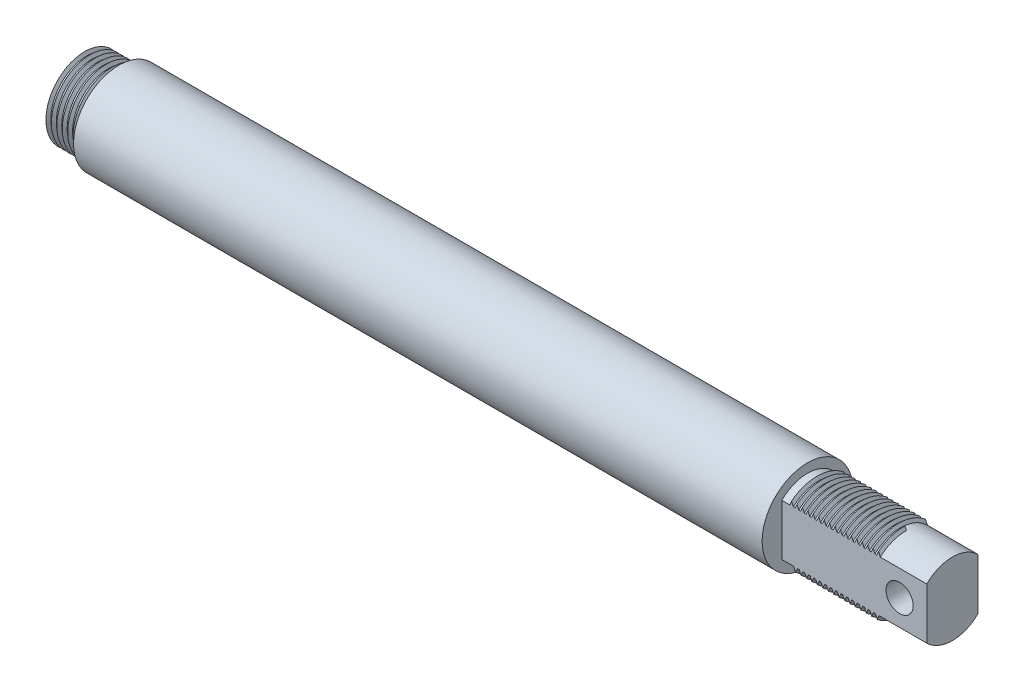
SolidWorks part; units mm, degrees
ref_plane "Front Plane" through (0, 0, 0) normal (0, 0, 1) x (1, 0, 0)
ref_plane "Top Plane" through (0, 0, 0) normal (0, 1, 0) x (1, 0, 0)
ref_plane "Right Plane" through (0, 0, 0) normal (1, 0, 0) x (0, 0, -1)
sketch "Sketch1" plane through (0, 0, 0) normal (1, 0, 0) x (0, 0, -1)
  circle A0 centre (0, 0) radius 25
extrude "Boss-Extrude1" add sketch "Sketch1" along normal blind 350
sketch "Sketch2" plane through (0, 0, 0) normal (-1, 0, 0) x (0, 0, 1)
  circle A0 centre (0, 0) radius 20
extrude "Cut-Extrude1" cut sketch "Sketch2" against normal blind 350
sketch "Sketch3" plane through (0, 0, 0) normal (-1, 0, 0) x (0, 0, 1)
  circle A0 centre (0, 0) radius 25
extrude "Boss-Extrude2" add sketch "Sketch3" along normal blind 15
sketch "Sketch5" plane through (350, 0, 0) normal (1, 0, 0) x (0, 0, -1)
  circle A0 centre (0, 0) radius 25
extrude "Boss-Extrude3" add sketch "Sketch5" along normal blind 15
sketch "Sketch6" plane through (365, 0, 0) normal (1, 0, 0) x (0, 0, -1)
  circle A0 centre (0, 0) radius 20
extrude "Boss-Extrude4" add sketch "Sketch6" along normal blind 80
sketch "Sketch7" plane through (445, 0, 0) normal (1, 0, 0) x (0, 0, -1)
  line L1 (-14.1328, -14.1514) -> (14.1328, -14.1514)
  line L2 (-14.1328, -14.1514) -> (-14.1328, 14.1514)
  line L3 (-14.1328, 14.1514) -> (14.1328, 14.1514)
  line L4 (14.1328, -14.1514) -> (14.1328, 14.1514)
  line L5 (-14.1328, -14.1514) -> (14.1328, 14.1514) construction
  line L6 (-14.1328, 14.1514) -> (14.1328, -14.1514) construction
  circle A0 centre (0, 0) radius 20 construction
  circle A1 centre (0, 0) radius 20
  point P0 (0, 0)
  circle M5 centre (0, 0) radius 20
extrude "Cut-Extrude2" cut sketch "Sketch7" against normal blind 80 contours L2 M5 | L4 M5 region at (445, 0, 16.512) region at (445, 0, -16.512)
sketch "Sketch8" plane through (0, 0, 14.1328) normal (0, 0, 1) x (1, 0, 0)
  circle A0 centre (430, 0) radius 7.5
extrude "Cut-Extrude3" cut sketch "Sketch8" against normal blind 70
ref_plane "Plane1" through (370, 0, 0) normal (1, 0, 0) x (0, 0, -1)
sketch "Sketch10" plane through (370, 0, 0) normal (1, 0, 0) x (0, 0, -1)
  circle A0 centre (0, 0) radius 20
curve "Helix/Spiral1" pitch 3 height 48.75 radius 20 left hand yes centre (370, 0, 0) axis (1, 0, 0) start towards (0, 0, 1)
sketch "Sketch12" plane through (0, 0, 0) normal (0, 0, 1) x (1, 0, 0)
  line L0 (445, 20) -> (365, 20) construction
  line L1 (418.75, 21.7) -> (417.2778, 19.15)
  line L2 (417.2778, 19.15) -> (420.2222, 19.15)
  line L3 (420.2222, 19.15) -> (418.75, 21.7)
  circle A0 centre (418.75, 20) radius 0.85 construction
  spline S0 degree 3 poles (370, 0) (370.0504, 2.1116) (370.152, 6.3652) (370.3037, 12.083) (370.4556, 16.595) (370.6075, 19.4405) (370.7593, 20.3362) (370.9112, 19.1916) (371.0631, 16.1217) (371.215, 11.4345) (371.3668, 5.6001) (371.5187, -0.7961) (371.6706, -7.1124) (371.8224, -12.7152) (371.9743, -17.0424) (372.1262, -19.6598) (372.278, -20.305) (372.4299, -18.9132) (372.5818, -15.624) (372.7336, -10.7673) (372.8855, -4.8305) (373.0374, 1.5909) (373.1893, 7.8527) (373.3411, 13.3268) (373.493, 17.4638) (373.6449, 19.8489) (373.7967, 20.2428) (373.9486, 18.6058) (374.1005, 15.1023) (374.2523, 10.0837) (374.4042, 4.0535) (374.5561, -2.3833) (374.7079, -8.5811) (374.8598, -13.9179) (375.0117, -17.8586) (375.1636, -20.0076) (375.3154, -20.1495) (375.4673, -18.2699) (375.6192, -14.5575) (375.771, -9.3847) (375.9229, -3.2703) (376.0748, 3.1721) (376.2266, 9.2962) (376.3785, 14.4878) (376.5304, 18.2259) (376.6822, 20.1356) (376.8341, 20.0253) (376.986, 17.906) (377.1379, 13.9904) (377.2897, 8.6712) (377.4416, 2.4821) (377.5935, -3.956) (377.7453, -9.9972) (377.8972, -15.0355) (378.0491, -18.5654) (378.2009, -20.2328) (378.3528, -19.8704) (378.5047, -17.5147) (378.6565, -13.4018) (378.8084, -7.9445) (378.9603, -1.6901) (379.1121, 4.7338) (379.264, 10.6828) (379.4159, 15.5601) (379.5678, 18.8764) (379.7196, 20.2989) (379.8715, 19.6851) (380.0234, 17.0965) (380.1752, 12.7927) (380.3271, 7.2055) (380.479, 0.8955) (380.6308, -5.5044) (380.7827, -11.352) (380.9346, -16.0608) (381.0864, -19.1584) (381.2383, -20.334) (381.3902, -19.4697) (381.5421, -16.6521) (381.6939, -12.164) (381.8458, -6.4556) (381.9977, -0.0995) (382.1495, 6.2665) (382.3014, 12.0039) (382.4533, 16.537) (382.6051, 19.4111) (382.757, 20.3379) (382.9089, 19.2244) (383.0607, 16.1822) (383.2126, 11.5167) (383.3645, 5.6957) (383.5164, -0.6966) (383.6682, -7.019) (383.8201, -12.6373) (383.972, -16.9878) (384.1238, -19.6341) (384.2757, -20.3106) (384.4276, -18.9496) (384.5794, -15.6875) (384.7313, -10.8517) (384.8832, -4.9272) (385.035, 1.4917) (385.1869, 7.7608) (385.3388, 13.2514) (385.4907, 17.4126) (385.6425, 19.827) (385.7944, 20.2522) (385.9463, 18.6458) (386.0981, 15.1688) (386.25, 10.17) (386.4019, 4.151) (386.5537, -2.2844) (386.7056, -8.4907) (386.8575, -13.8452) (387.0093, -17.8107) (387.1612, -19.9894) (387.3131, -20.1628) (387.465, -18.3134) (387.6168, -14.6268) (387.7687, -9.4728) (387.9206, -3.3685) (388.0724, 3.0737) (388.2243, 9.2076) (388.3762, 14.4178) (388.528, 18.1815) (388.6799, 20.1213) (388.8318, 20.0425) (388.9836, 17.953) (389.1355, 14.0624) (389.2874, 8.7611) (389.4393, 2.5809) (389.5911, -3.8583) (389.743, -9.9104) (389.8949, -14.9682) (390.0467, -18.5245) (390.1986, -20.2223) (390.3505, -19.8915) (390.5023, -17.5651) (390.6542, -13.4765) (390.8061, -8.036) (390.9579, -1.7893) (391.1098, 4.6369) (391.2617, 10.5979) (391.4136, 15.4958) (391.5654, 18.8391) (391.7173, 20.2924) (391.8692, 19.7099) (392.021, 17.1502) (392.1729, 12.8699) (392.3248, 7.2985) (392.4766, 0.9949) (392.6285, -5.4085) (392.7804, -11.2693) (392.9322, -15.9996) (393.0841, -19.1248) (393.236, -20.3313) (393.3879, -19.4982) (393.5397, -16.7091) (393.6916, -12.2436) (393.8435, -6.5499) (393.9953, -0.1991) (394.1472, 6.1717) (394.2991, 11.9234) (394.4509, 16.4788) (394.6028, 19.3811) (394.7547, 20.3391) (394.9065, 19.2566) (395.0584, 16.2423) (395.2103, 11.5986) (395.3621, 5.7912) (395.514, -0.5971) (395.6659, -6.9255) (395.8178, -12.5592) (395.9696, -16.9329) (396.1215, -19.6078) (396.2734, -20.3157) (396.4252, -18.9855) (396.5771, -15.7507) (396.729, -10.9357) (396.8808, -5.0237) (397.0327, 1.3924) (397.1846, 7.6687) (397.3364, 13.1757) (397.4883, 17.361) (397.6402, 19.8045) (397.7921, 20.2612) (397.9439, 18.6853) (398.0958, 15.2349) (398.2477, 10.2561) (398.3995, 4.2484) (398.5514, -2.1855) (398.7033, -8.4002) (398.8551, -13.7721) (399.007, -17.7624) (399.1589, -19.9708) (399.3107, -20.1757) (399.4626, -18.3565) (399.6145, -14.6958) (399.7664, -9.5608) (399.9182, -3.4667) (400.0701, 2.9753) (400.222, 9.1187) (400.3738, 14.3474) (400.5257, 18.1367) (400.6776, 20.1065) (400.8294, 20.0592) (400.9813, 17.9996) (401.1332, 14.1342) (401.285, 8.8508) (401.4369, 2.6796) (401.5888, -3.7605) (401.7407, -9.8233) (401.8925, -14.9007) (402.0444, -18.4832) (402.1963, -20.2114) (402.3481, -19.912) (402.5, -17.615) (402.6519, -13.5509) (402.8037, -8.1273) (402.9556, -1.8884) (403.1075, 4.54) (403.2593, 10.5129) (403.4112, 15.4311) (403.5631, 18.8013) (403.715, 20.2853) (403.8668, 19.7343) (404.0187, 17.2035) (404.1706, 12.9468) (404.3224, 7.3913) (404.4743, 1.0943) (404.6262, -5.3125) (404.778, -11.1863) (404.9299, -15.9379) (405.0818, -19.0906) (405.2336, -20.3282) (405.3855, -19.5263) (405.5374, -16.7656) (405.6893, -12.323) (405.8411, -6.644) (405.993, -0.2986) (406.1449, 6.0768) (406.2967, 11.8426) (406.4486, 16.4203) (406.6005, 19.3507) (406.7523, 20.3398) (406.9042, 19.2885) (407.0561, 16.302) (407.2079, 11.6802) (407.3598, 5.8866) (407.5117, -0.4976) (407.6636, -6.8319) (407.8154, -12.4807) (407.9673, -16.8775) (408.1192, -19.5811) (408.271, -20.3204) (408.4229, -19.021) (408.5748, -15.8135) (408.7266, -11.0195) (408.8785, -5.12) (409.0304, 1.2931) (409.1822, 7.5764) (409.3341, 13.0998) (409.486, 17.3089) (409.6379, 19.7816) (409.7897, 20.2698) (409.9416, 18.7244) (410.0935, 15.3007) (410.2453, 10.342) (410.3972, 4.3457) (410.5491, -2.0865) (410.7009, -8.3094) (410.8528, -13.6987) (411.0047, -17.7137) (411.1565, -19.9517) (411.3084, -20.1881) (411.4603, -18.3992) (411.6121, -14.7645) (411.764, -9.6485) (411.9159, -3.5647) (412.0678, 2.8768) (412.2196, 9.0297) (412.3715, 14.2767) (412.5234, 18.0914) (412.6752, 20.0912) (412.8271, 20.0755) (412.979, 18.0457) (413.1308, 14.2056) (413.2827, 8.9404) (413.4346, 2.7782) (413.5864, -3.6626) (413.7383, -9.7361) (413.8902, -14.8327) (414.0421, -18.4414) (414.1939, -20.2) (414.3458, -19.9321) (414.4977, -17.6646) (414.6495, -13.625) (414.8014, -8.2185) (414.9533, -1.9875) (415.1051, 4.4429) (415.257, 10.4275) (415.4089, 15.3661) (415.5607, 18.7631) (415.7126, 20.2778) (415.8645, 19.7582) (416.0164, 17.2564) (416.1682, 13.0235) (416.3201, 7.484) (416.472, 1.1937) (416.6238, -5.2163) (416.7757, -11.103) (416.9276, -15.8759) (417.0794, -19.0561) (417.2313, -20.3245) (417.3832, -19.554) (417.535, -16.8218) (417.6869, -12.402) (417.8388, -6.738) (417.9907, -0.3981) (418.1425, 5.9818) (418.2944, 11.7615) (418.4463, 16.3614) (418.598, 19.3198) (418.6996, 20) (418.75, 20) knots 0 0 0 0 0.003115 0.006231 0.009346 0.012461 0.015576 0.018692 0.021807 0.024922 0.028037 0.031153 0.034268 0.037383 0.040498 0.043614 0.046729 0.049844 0.05296 0.056075 0.05919 0.062305 0.065421 0.068536 0.071651 0.074766 0.077882 0.080997 0.084112 0.087227 0.090343 0.093458 0.096573 0.099688 0.102804 0.105919 0.109034 0.11215 0.115265 0.11838 0.121495 0.124611 0.127726 0.130841 0.133956 0.137072 0.140187 0.143302 0.146417 0.149533 0.152648 0.155763 0.158879 0.161994 0.165109 0.168224 0.17134 0.174455 0.17757 0.180685 0.183801 0.186916 0.190031 0.193146 0.196262 0.199377 0.202492 0.205607 0.208723 0.211838 0.214953 0.218069 0.221184 0.224299 0.227414 0.23053 0.233645 0.23676 0.239875 0.242991 0.246106 0.249221 0.252336 0.255452 0.258567 0.261682 0.264798 0.267913 0.271028 0.274143 0.277259 0.280374 0.283489 0.286604 0.28972 0.292835 0.29595 0.299065 0.302181 0.305296 0.308411 0.311526 0.314642 0.317757 0.320872 0.323988 0.327103 0.330218 0.333333 0.336449 0.339564 0.342679 0.345794 0.34891 0.352025 0.35514 0.358255 0.361371 0.364486 0.367601 0.370717 0.373832 0.376947 0.380062 0.383178 0.386293 0.389408 0.392523 0.395639 0.398754 0.401869 0.404984 0.4081 0.411215 0.41433 0.417445 0.420561 0.423676 0.426791 0.429907 0.433022 0.436137 0.439252 0.442368 0.445483 0.448598 0.451713 0.454829 0.457944 0.461059 0.464174 0.46729 0.470405 0.47352 0.476636 0.479751 0.482866 0.485981 0.489097 0.492212 0.495327 0.498442 0.501558 0.504673 0.507788 0.510903 0.514019 0.517134 0.520249 0.523364 0.52648 0.529595 0.53271 0.535826 0.538941 0.542056 0.545171 0.548287 0.551402 0.554517 0.557632 0.560748 0.563863 0.566978 0.570093 0.573209 0.576324 0.579439 0.582555 0.58567 0.588785 0.5919 0.595016 0.598131 0.601246 0.604361 0.607477 0.610592 0.613707 0.616822 0.619938 0.623053 0.626168 0.629283 0.632399 0.635514 0.638629 0.641745 0.64486 0.647975 0.65109 0.654206 0.657321 0.660436 0.663551 0.666667 0.669782 0.672897 0.676012 0.679128 0.682243 0.685358 0.688474 0.691589 0.694704 0.697819 0.700935 0.70405 0.707165 0.71028 0.713396 0.716511 0.719626 0.722741 0.725857 0.728972 0.732087 0.735202 0.738318 0.741433 0.744548 0.747664 0.750779 0.753894 0.757009 0.760125 0.76324 0.766355 0.76947 0.772586 0.775701 0.778816 0.781931 0.785047 0.788162 0.791277 0.794393 0.797508 0.800623 0.803738 0.806854 0.809969 0.813084 0.816199 0.819315 0.82243 0.825545 0.82866 0.831776 0.834891 0.838006 0.841121 0.844237 0.847352 0.850467 0.853583 0.856698 0.859813 0.862928 0.866044 0.869159 0.872274 0.875389 0.878505 0.88162 0.884735 0.88785 0.890966 0.894081 0.897196 0.900312 0.903427 0.906542 0.909657 0.912773 0.915888 0.919003 0.922118 0.925234 0.928349 0.931464 0.934579 0.937695 0.94081 0.943925 0.94704 0.950156 0.953271 0.956386 0.959502 0.962617 0.965732 0.968847 0.971963 0.975078 0.978193 0.981308 0.984424 0.987539 0.990654 0.993769 0.996885 1 1 1 1 construction
sweep "Sweep1" add profiles "Sketch12" path "Helix/Spiral1"
sketch "Sketch13" plane through (445, 0, 0) normal (1, 0, 0) x (0, 0, -1)
  line L1 (14.1328, 26.4625) -> (-14.1328, 26.4625)
  line L2 (14.1328, 26.4625) -> (14.1328, -26.4625)
  line L3 (14.1328, -26.4625) -> (-14.1328, -26.4625)
  line L4 (-14.1328, 26.4625) -> (-14.1328, -26.4625)
  line L5 (14.1328, 26.4625) -> (-14.1328, -26.4625) construction
  line L6 (14.1328, -26.4625) -> (-14.1328, 26.4625) construction
  circle A0 centre (0, 0) radius 30
  line M2 (14.1328, -14.1514) -> (14.1328, 14.1514)
  line M4 (-14.1328, 14.1514) -> (-14.1328, -14.1514)
extrude "Cut-Extrude4" cut sketch "Sketch13" against normal blind 80 contours L4 A0 M4 | L2 A0 M2 region at (445, 0, -20.6499) region at (445, 0, 20.6499)
sketch "Sketch14" plane through (-15, 0, 0) normal (-1, 0, 0) x (0, 0, 1)
  circle A0 centre (0, 0) radius 20
extrude "Boss-Extrude5" add sketch "Sketch14" along normal blind 20
sketch "Sketch15" plane through (-35, 0, 0) normal (-1, 0, 0) x (0, 0, 1)
  circle A0 centre (0, 0) radius 20
curve "Helix/Spiral2" pitch 3 height 17.25 radius 20 centre (-35, 0, 0) axis (1, 0, 0) start towards (0, 0, -1)
sketch "Sketch16" plane through (0, 0, 0) normal (0, 0, 1) x (1, 0, 0)
  line L0 (-35, -20) -> (-15, -20) construction
  line L1 (-17.75, -21.7) -> (-16.2778, -19.15)
  line L2 (-16.2778, -19.15) -> (-19.2222, -19.15)
  line L3 (-19.2222, -19.15) -> (-17.75, -21.7)
  circle A0 centre (-17.75, -20) radius 0.85 construction
  spline S0 degree 3 poles (-35, 0) (-34.9493, 2.1224) (-34.8472, 6.3982) (-34.6947, 12.1389) (-34.542, 16.6558) (-34.3894, 19.4829) (-34.2367, 20.3358) (-34.0841, 19.1275) (-33.9314, 15.9806) (-33.7788, 11.214) (-33.6261, 5.3108) (-33.4735, -1.1306) (-33.3208, -7.4574) (-33.1681, -13.0284) (-33.0155, -17.279) (-32.8628, -19.7782) (-32.7102, -20.2729) (-32.5575, -18.7129) (-32.4049, -15.2563) (-32.2522, -10.2533) (-32.0996, -4.2112) (-31.9469, 2.2577) (-31.7942, 8.4978) (-31.6416, 13.8766) (-31.4889, 17.849) (-31.3363, 20.0124) (-31.1836, 20.1474) (-31.031, 18.2404) (-30.8783, 14.4848) (-30.7257, 9.261) (-30.573, 3.0986) (-30.4204, -3.3778) (-30.2677, -9.5119) (-30.115, -14.6819) (-29.9624, -18.3639) (-29.8097, -20.1846) (-29.6571, -19.9596) (-29.5044, -17.7116) (-29.3518, -13.6685) (-29.1991, -8.24) (-29.0465, -1.9764) (-28.8938, 4.4875) (-28.7412, 10.4966) (-28.5885, 15.4418) (-28.4358, 18.822) (-28.2832, 20.2945) (-28.1305, 19.7101) (-27.9779, 17.1281) (-27.8252, 12.81) (-27.6726, 7.1936) (-27.5199, 0.8481) (-27.3673, -5.5833) (-27.2146, -11.4489) (-27.0619, -16.154) (-26.9093, -19.222) (-26.7566, -20.3417) (-26.604, -19.3997) (-26.4513, -16.4915) (-26.2987, -11.9119) (-26.146, -6.1249) (-25.9934, 0.2828) (-25.8407, 6.6619) (-25.6881, 12.3657) (-25.5354, 16.8163) (-25.3827, 19.5625) (-25.2301, 20.326) (-25.0774, 19.0293) (-24.9248, 15.804) (-24.7721, 10.977) (-24.6195, 5.0373) (-24.4668, -1.4128) (-24.3142, -7.7198) (-24.1615, -13.2444) (-24.0088, -17.4266) (-23.8562, -19.8425) (-23.7035, -20.2474) (-23.5509, -18.6002) (-23.3982, -15.0677) (-23.2456, -10.0081) (-23.0929, -3.9342) (-22.9403, 2.5385) (-22.7876, 8.7539) (-22.635, 14.0821) (-22.4823, 17.983) (-22.3296, 20.0613) (-22.177, 20.1063) (-22.0243, 18.1135) (-21.8717, 14.2848) (-21.719, 9.0083) (-21.5664, 2.8188) (-21.4137, -3.6563) (-21.2611, -9.761) (-21.1084, -14.8763) (-20.9558, -18.4838) (-20.8031, -20.218) (-20.6504, -19.903) (-20.4978, -17.5708) (-20.3451, -13.4577) (-20.1925, -7.9807) (-20.0398, -1.6948) (-19.8872, 4.7629) (-19.7345, 10.7378) (-19.5819, 15.6245) (-19.4292, 18.9275) (-19.2765, 20.3122) (-19.1239, 19.6382) (-18.9712, 16.9738) (-18.8186, 12.5891) (-18.6659, 6.9284) (-18.5133, 0.5655) (-18.3606, -5.8547) (-18.208, -11.6815) (-18.0553, -16.3244) (-17.9028, -19.3127) (-17.8007, -20) (-17.75, -20) knots 0 0 0 0 0.00885 0.017699 0.026549 0.035398 0.044248 0.053097 0.061947 0.070796 0.079646 0.088496 0.097345 0.106195 0.115044 0.123894 0.132743 0.141593 0.150442 0.159292 0.168142 0.176991 0.185841 0.19469 0.20354 0.212389 0.221239 0.230088 0.238938 0.247788 0.256637 0.265487 0.274336 0.283186 0.292035 0.300885 0.309735 0.318584 0.327434 0.336283 0.345133 0.353982 0.362832 0.371681 0.380531 0.389381 0.39823 0.40708 0.415929 0.424779 0.433628 0.442478 0.451327 0.460177 0.469027 0.477876 0.486726 0.495575 0.504425 0.513274 0.522124 0.530973 0.539823 0.548673 0.557522 0.566372 0.575221 0.584071 0.59292 0.60177 0.610619 0.619469 0.628319 0.637168 0.646018 0.654867 0.663717 0.672566 0.681416 0.690265 0.699115 0.707965 0.716814 0.725664 0.734513 0.743363 0.752212 0.761062 0.769912 0.778761 0.787611 0.79646 0.80531 0.814159 0.823009 0.831858 0.840708 0.849558 0.858407 0.867257 0.876106 0.884956 0.893805 0.902655 0.911504 0.920354 0.929204 0.938053 0.946903 0.955752 0.964602 0.973451 0.982301 0.99115 1 1 1 1 construction
sweep "Sweep2" add profiles "Sketch16" path "Helix/Spiral2"
sketch "Sketch17" plane through (0, 0, 0) normal (0, 1, 0) x (1, 0, 0)
  line L1 (-35, -20) -> (-37.7667, -20)
  line L2 (-35, -20) -> (-35, 22.7682)
  line L3 (-35, 22.7682) -> (-37.7667, 22.7682)
  line L4 (-37.7667, -20) -> (-37.7667, 22.7682)
extrude "Cut-Extrude8" cut sketch "Sketch17" against normal blind 40 and the other way blind 40
sketch "Sketch18" plane through (-35, 0, 0) normal (-1, 0, 0) x (0, 0, 1)
  circle A0 centre (0, 0) radius 5
extrude "Cut-Extrude9" cut sketch "Sketch18" against normal blind 90
